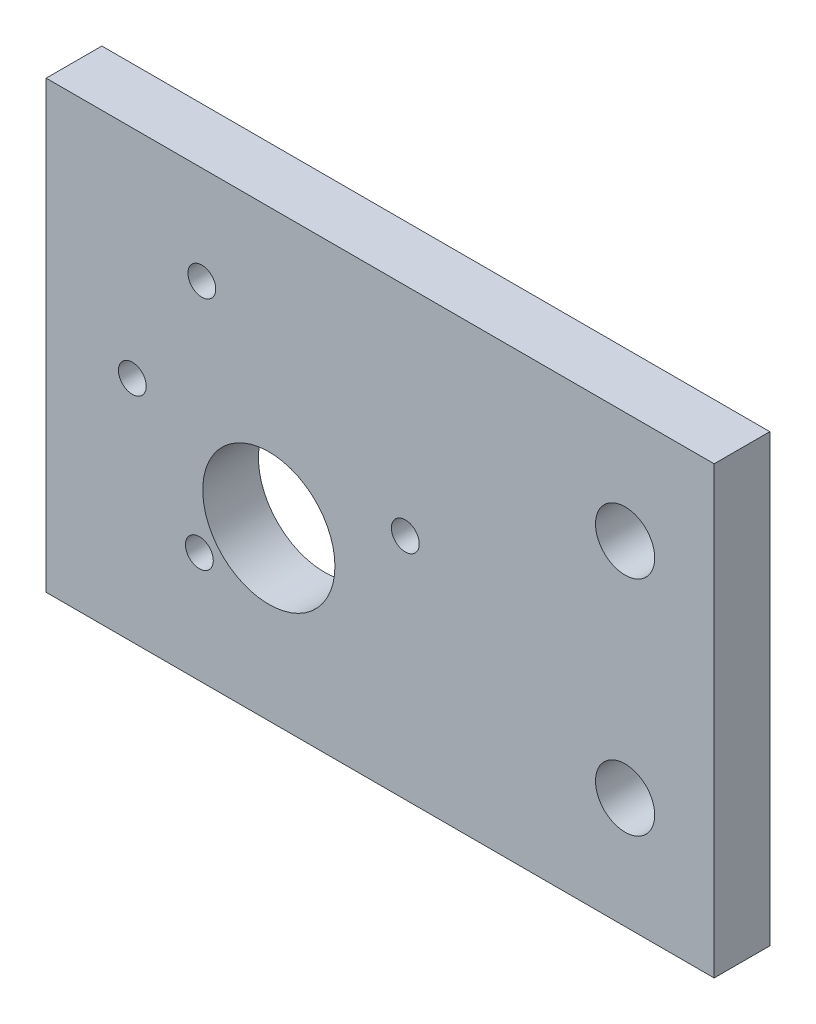
SolidWorks part; units mm, degrees
material "1060 Alloy"
ref_plane "Front" through (0, 0, 0) normal (0, 0, 1) x (1, 0, 0)
ref_plane "Top" through (0, 0, 0) normal (0, 1, 0) x (1, 0, 0)
ref_plane "Right" through (0, 0, 0) normal (1, 0, 0) x (0, 0, -1)
sketch "Sketch1" plane through (0, 0, 0) normal (0, 0, 1) x (1, 0, 0)
  line L1 (-38.1, 25.4) -> (38.1, 25.4)
  line L2 (-38.1, 25.4) -> (-38.1, -25.4)
  line L3 (-38.1, -25.4) -> (38.1, -25.4)
  line L4 (38.1, 25.4) -> (38.1, -25.4)
  line L5 (-38.1, 25.4) -> (38.1, -25.4) construction
  line L6 (-38.1, -25.4) -> (38.1, 25.4) construction
  point P0 (0, 0)
  dimension "D1" = 76.2
  dimension "D2" = 50.8
extrude "Boss-Extrude1" add sketch "Sketch1" along normal blind 6.35
hole_wizard "19/32 (0.59375) Diameter Hole1" positions "Sketch3" profile "Sketch4" hole size "19/32" standard "ANSI Inch" end condition through all
sketch "Sketch3" plane through (0, 0, 6.35) normal (0, 0, 1) x (1, 0, 0)
  line L0 (-38.1, 25.4) -> (-38.1, -25.4) construction
  line L1 (38.1, 25.4) -> (-38.1, 25.4) construction
  point P0 (-12.7, -6.35)
  dimension "D1" = 25.4
  dimension "D2" = 31.75
sketch "Sketch4" plane through (-12.7, -6.35, 6.35) normal (1, 0, 0) x (0, -1, 0)
  line L0 (0, 0) -> (0, 6.35)
  line L1 (0, 6.35) -> (7.5406, 6.35)
  line L2 (7.5406, 6.35) -> (7.5406, 0)
  line L5 (7.5406, 0) -> (0, 0)
  line L11 (0, -6.35) -> (0, 107.95) construction
  dimension "Thru Hole Dia." = 15.0812
  dimension "Thru Hole Depth" = 6.35
sketch "Sketch5" plane through (0, 0, 6.35) normal (0, 0, 1) x (1, 0, 0)
  circle A0 centre (-12.7, 0.6604) radius 15.5702 construction
  circle A1 centre (-12.7, -6.35) radius 7.5406 construction
  circle A2 centre (-12.7, -6.35) radius 7.5406 construction
  dimension "D1" = 31.1404
  dimension "D2" = 7.0104
hole_wizard "1/8 (0.125) Diameter Hole1" positions "Sketch6" profile "Sketch7" hole size "1/8" standard "ANSI Inch" end condition through all
sketch "Sketch6" plane through (0, 0, 6.35) normal (0, 0, 1) x (1, 0, 0)
  circle A0 centre (-12.7, 0.6604) radius 15.5702 construction
  point P0 (-20.3454, 14.2243)
  point P2 (-28.2702, 0.6604)
  point P4 (-20.6248, -12.7422)
  point P6 (2.8702, 0.6604)
  dimension "D1" = 7.6454
  dimension "D2" = 7.9248
sketch "Sketch7" plane through (-20.3454, 14.2243, 6.35) normal (1, 0, 0) x (0, -1, 0)
  line L0 (0, 0) -> (0, 6.35)
  line L1 (0, 6.35) -> (1.5875, 6.35)
  line L2 (1.5875, 6.35) -> (1.5875, 0)
  line L5 (1.5875, 0) -> (0, 0)
  line L11 (0, -6.35) -> (0, 107.95) construction
  dimension "Thru Hole Dia." = 3.175
  dimension "Thru Hole Depth" = 6.35
hole_wizard "H (0.266) Diameter Hole1" positions "Sketch8" profile "Sketch9" hole size "H" standard "ANSI Inch" end condition through all
sketch "Sketch8" plane through (0, 0, 6.35) normal (0, 0, 1) x (1, 0, 0)
  line L0 (38.1, -25.4) -> (38.1, 25.4) construction
  line L1 (38.1, 25.4) -> (-38.1, 25.4) construction
  point P0 (27.94, 12.7)
  point P2 (27.94, -12.7)
  dimension "D1" = 10.16
  dimension "D2" = 12.7
  dimension "D3" = 38.1
sketch "Sketch9" plane through (27.94, 12.7, 6.35) normal (1, 0, 0) x (0, -1, 0)
  line L0 (0, 0) -> (0, 6.35)
  line L1 (0, 6.35) -> (3.3782, 6.35)
  line L2 (3.3782, 6.35) -> (3.3782, 0)
  line L5 (3.3782, 0) -> (0, 0)
  line L11 (0, -6.35) -> (0, 107.95) construction
  dimension "Thru Hole Dia." = 6.7564
  dimension "Thru Hole Depth" = 6.35
